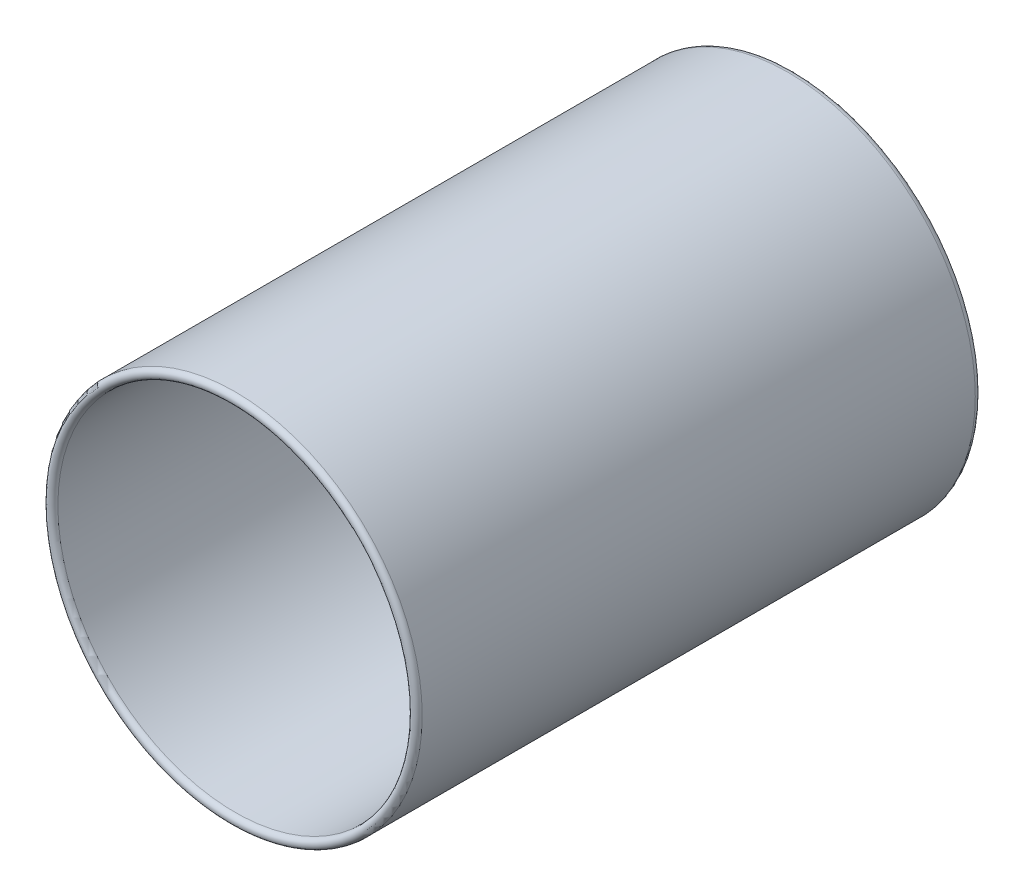
SolidWorks part; units mm, degrees
material "Glass"
ref_plane "Front Plane" through (0, 0, 0) normal (0, 0, 1) x (1, 0, 0)
ref_plane "Top Plane" through (0, 0, 0) normal (0, 1, 0) x (1, 0, 0)
ref_plane "Right Plane" through (0, 0, 0) normal (1, 0, 0) x (0, 0, -1)
sketch "Sketch1" plane through (0, 0, 0) normal (0, 0, 1) x (1, 0, 0)
  circle A0 centre (0, 0) radius 28.5
  dimension "D1" = 57
extrude "Boss-Extrude1" add sketch "Sketch1" along normal blind 86
sketch "Sketch2" plane through (0, 0, 86) normal (0, 0, 1) x (1, 0, 0)
  circle A0 centre (0, 0) radius 27
  dimension "D1" = 54
extrude "Cut-Extrude1" cut sketch "Sketch2" against normal blind 84
fillet "Fillet1" radius 1 1 edges at (28.5, 0, 0)
fillet "Fillet2" 2 edges at (28.5, 0, 86) (27, 0, 86) type full round first side face at (28.5, 0, 1) second side face at (27, 0, 2) middle face at (27, 0, 86)
